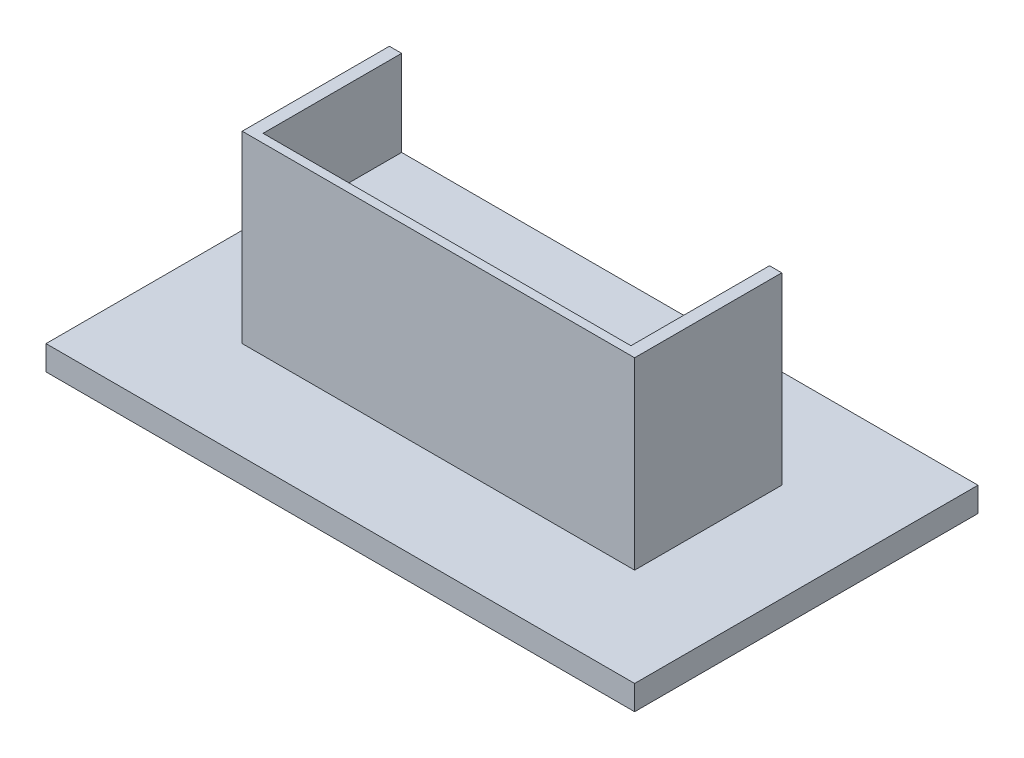
SolidWorks part; units mm, degrees
ref_plane "Front Plane" through (0, 0, 0) normal (0, 0, 1) x (1, 0, 0)
ref_plane "Top Plane" through (0, 0, 0) normal (0, 1, 0) x (1, 0, 0)
ref_plane "Right Plane" through (0, 0, 0) normal (1, 0, 0) x (0, 0, -1)
sketch "Sketch1" plane through (0, 0, 0) normal (0, 0, 1) x (1, 0, 0)
  line L1 (-120000, -5000) -> (120000, -5000)
  line L2 (-120000, -5000) -> (-120000, 5000)
  line L3 (-120000, 5000) -> (120000, 5000)
  line L4 (120000, -5000) -> (120000, 5000)
  line L5 (-120000, -5000) -> (120000, 5000) construction
  line L6 (-120000, 5000) -> (120000, -5000) construction
  point P0 (0, 0)
  dimension "D1" = 10000
  dimension "D2" = 240000
extrude "Boss-Extrude1" add sketch "Sketch1" against normal blind 70000 and the other way blind 70000
sketch "Sketch2" plane through (0, 5000, 0) normal (0, 1, 0) x (1, 0, 0)
  line L1 (-80000, -30000) -> (80000, -30000)
  line L2 (-80000, -30000) -> (-80000, 30000)
  line L3 (-80000, 30000) -> (80000, 30000)
  line L4 (80000, -30000) -> (80000, 30000)
  line L5 (-80000, -30000) -> (80000, 30000) construction
  line L6 (-80000, 30000) -> (80000, -30000) construction
  point P0 (0, 0)
  dimension "D1" = 60000
  dimension "D2" = 160000
extrude "Boss-Extrude2" add sketch "Sketch2" along normal blind 40000
sketch "Sketch3" plane through (0, 45000, 0) normal (0, 1, 0) x (1, 0, 0)
  line L0 (80000, -30000) -> (80000, 30000) construction
  line L1 (-80000, -30000) -> (80000, -30000)
  line L2 (-80000, -30000) -> (-80000, -26500)
  line L3 (-80000, -26500) -> (80000, -26500)
  line L4 (80000, -30000) -> (80000, -26500)
  dimension "D1" = 3500
extrude "Boss-Extrude3" add sketch "Sketch3" along normal blind 35000
sketch "Sketch4" plane through (0, 45000, 0) normal (0, 1, 0) x (1, 0, 0)
  line L0 (80000, 30000) -> (-80000, 30000) construction
  line L1 (-80000, -26500) -> (-75000, -26500)
  line L2 (-80000, -26500) -> (-80000, 30000)
  line L3 (-80000, 30000) -> (-75000, 30000)
  line L4 (-75000, -26500) -> (-75000, 30000)
  line L6 (80000, -26500) -> (75000, -26500)
  line L7 (80000, -26500) -> (80000, 30000)
  line L8 (80000, 30000) -> (75000, 30000)
  line L9 (75000, -26500) -> (75000, 30000)
  dimension "D1" = 5000
  dimension "D2" = 5000
extrude "Boss-Extrude4" add sketch "Sketch4" along normal blind 35000
sketch "Sketch5" plane through (0, 0, 30000) normal (0, 0, 1) x (1, 0, 0)
  line L0 (-52179.7107, 65000) -> (80000, 65000) construction
  line L1 (-80000, 5000) -> (80000, 5000) construction
  line L2 (80000, 80000) -> (80000, 5000) construction
  circle A0 centre (-52179.7107, 65000) radius 3625
  circle A1 centre (-60679.7107, 65000) radius 1500
  circle A2 centre (-43679.7107, 65000) radius 1500
  dimension "D1" = 7250
  dimension "D2" = 60000
  dimension "D3" = 3000
  dimension "D4" = 3000
  dimension "D5" = 8500
  dimension "D6" = 8500
